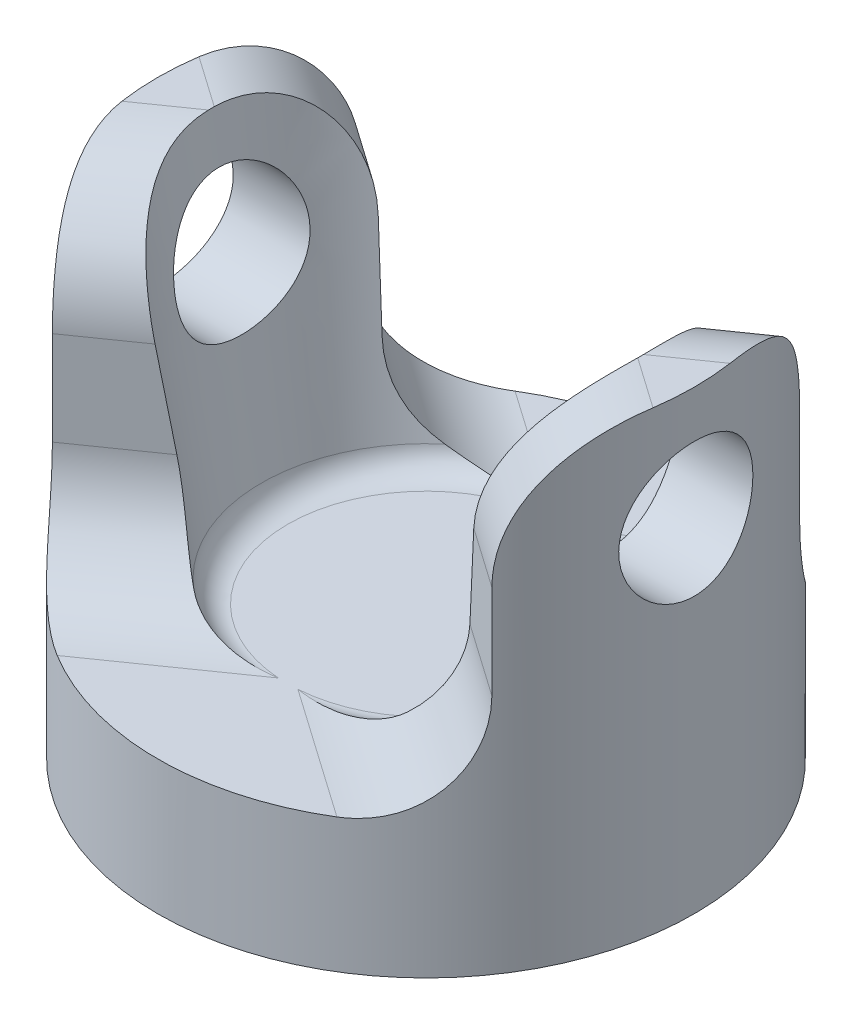
SolidWorks part; units mm, degrees
ref_plane "Front Plane" through (0, 0, 0) normal (0, 0, 1) x (1, 0, 0)
ref_plane "Top Plane" through (0, 0, 0) normal (0, 1, 0) x (1, 0, 0)
ref_plane "Right Plane" through (0, 0, 0) normal (1, 0, 0) x (0, 0, -1)
sketch "Sketch1" plane through (0, 0, 0) normal (0, 1, 0) x (1, 0, 0)
  circle A0 centre (0, 0) radius 10
  dimension "D1" = 20
extrude "Boss-Extrude1" add sketch "Sketch1" along normal blind 5
sketch "Sketch3" plane through (0, 0, 0) normal (0, 0, 1) x (1, 0, 0)
  line L0 (-10, 5) -> (-10, 0) construction
  line L1 (-10, 5) -> (-10, 0) construction
  line L2 (10, 0) -> (10, 5) construction
  line L3 (10, 0) -> (10, 5) construction
  line L4 (0, 0) -> (0, 13.5762) construction
  line L5 (-10, 5) -> (-10, 17)
  line L6 (-10, 17) -> (-8, 17)
  line L7 (-8, 17) -> (-6, 5)
  line L8 (10, 5) -> (-10, 5) construction
  line L9 (-6, 5) -> (-10, 5)
  dimension "D1" = 12
  dimension "D2" = 2
  dimension "D3" = 4
revolve "Revolve1" add sketch "Sketch3" angle 70 mid plane about L4
fillet "Fillet2" radius 4 2 edges at (-6.5532, 5, -4.5886) (-6.5532, 5, 4.5886)
fillet "Fillet1" radius 4.5 2 edges at (-7.3724, 17, -5.1622) (-7.3724, 17, 5.1622)
fillet "Fillet3" radius 1 1 edges at (-6, 5, 0)
mirror "Mirror3" about plane through (0, 0, 0) normal (1, 0, 0) of "Fillet3", "Fillet1", "Revolve1", "Fillet2"
ref_plane "Plane4" through (10, 0, 0) normal (1, 0, 0) x (0, 0, -1)
sketch "Sketch6" plane through (10, 0, 0) normal (1, 0, 0) x (0, 0, -1)
  line L0 (0, 17) -> (0, 0) construction
  line L1 (1.436, 17) -> (-1.436, 17) construction
  circle A0 centre (0, 12.75) radius 4.25 construction
  circle A1 centre (0, 12.75) radius 2.5
  point P5 (0, 8.5)
  dimension "D1" = 5
extrude "Cut-Extrude3" cut sketch "Sketch6" against normal through all
